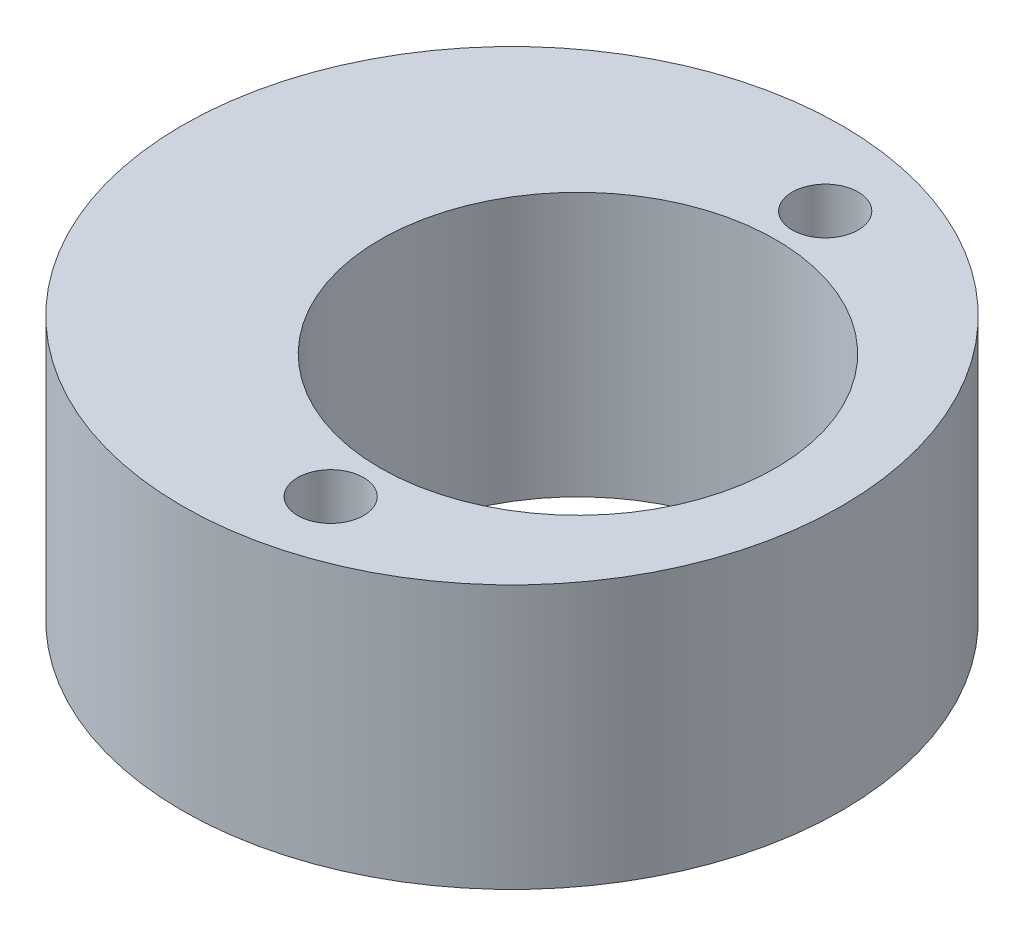
SolidWorks part; units mm, degrees
ref_plane "Front Plane" through (0, 0, 0) normal (0, 0, 1) x (1, 0, 0)
ref_plane "Top Plane" through (0, 0, 0) normal (0, 1, 0) x (1, 0, 0)
ref_plane "Right Plane" through (0, 0, 0) normal (1, 0, 0) x (0, 0, -1)
sketch "Sketch1" plane through (0, 0, 0) normal (0, 1, 0) x (1, 0, 0)
  line L0 (-1, 0) -> (0, 0) construction
  circle A0 centre (0, 0) radius 3
  circle A1 centre (-1, 0) radius 5
  dimension "D1" = 6
  dimension "D2" = 10
  dimension "D3" = 1
extrude "Boss-Extrude1" add sketch "Sketch1" along normal blind 4
sketch "Sketch2" plane through (0, 4, 0) normal (0, 1, 0) x (1, 0, 0)
  line L0 (0, 3.75) -> (0, -3.75) construction
  circle A0 centre (0, 3.75) radius 0.5
  circle A1 centre (0, -3.75) radius 0.5
  point P4 (0, 0)
  dimension "D1" = 1
  dimension "D2" = 1
  dimension "D3" = 0
  dimension "D4" = 7.5
extrude "Cut-Extrude1" cut sketch "Sketch2" against normal through all
